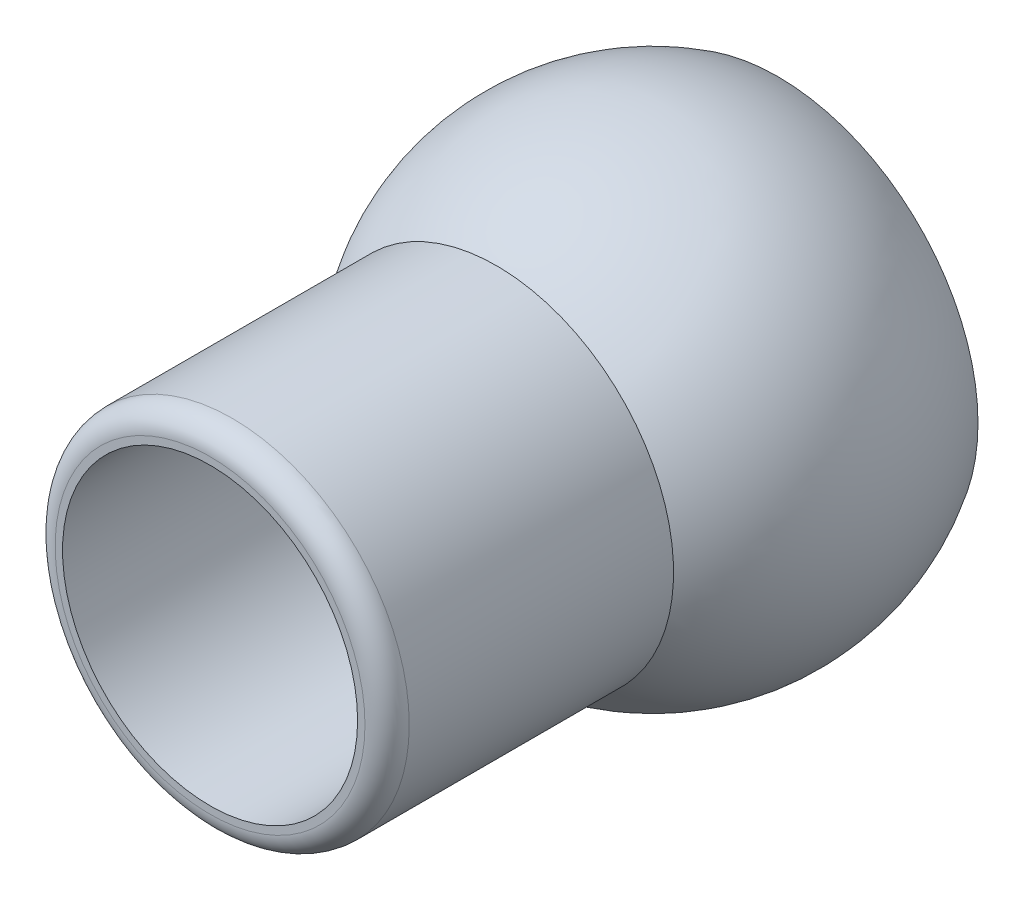
SolidWorks part; units mm, degrees
ref_plane "前视基准面" through (0, 0, 0) normal (0, 0, 1) x (1, 0, 0)
ref_plane "上视基准面" through (0, 0, 0) normal (0, 1, 0) x (1, 0, 0)
ref_plane "右视基准面" through (0, 0, 0) normal (1, 0, 0) x (0, 0, -1)
sketch "草图1" plane through (0, 0, 0) normal (0, 0, 1) x (1, 0, 0)
  line L0 (0, 16) -> (0, -16)
  arc A0 (0, -16) -> (0, 16) centre (0, 0) ccw
revolve "旋转1" add sketch "草图1" angle 360 about L0
sketch "草图2" plane through (0, 0, 0) normal (0, 0, 1) x (1, 0, 0)
  line L0 (0, 14) -> (0, -14)
  arc A0 (0, -14) -> (0, 14) centre (0, 0) ccw
revolve "切除-旋转1" cut sketch "草图2" angle 360 about L0
sketch "草图3" plane through (0, 0, 0) normal (0, 0, 1) x (1, 0, 0)
  circle A0 centre (0, 0) radius 12
extrude "凸台-拉伸2" add sketch "草图3" along normal blind 30
sketch "草图4" plane through (0, 0, 0) normal (0, 0, 1) x (1, 0, 0)
  circle A0 centre (0, 0) radius 10
extrude "切除-拉伸2" cut sketch "草图4" against normal blind 23 and the other way blind 30
sketch "草图6" plane through (0, 0, 0) normal (0, 0, 1) x (1, 0, 0)
  line L0 (0, 14) -> (0, -14)
  arc A0 (0, -14) -> (0, 14) centre (0, 0) ccw
revolve "切除-旋转2" cut sketch "草图6" angle 360 about L0
fillet "圆角1" radius 1.5 1 edges at (12, 0, 30)
sketch "草图7" plane through (0, 0, 0) normal (1, 0, 0) x (0, 0, -1)
  line L0 (0, 0) -> (12.49, 0)
  line L1 (12.49, -10) -> (12.49, 10) construction
  line L2 (12.49, 0) -> (7.49, 0)
  line L3 (7.49, 0) -> (7.49, -16.6991)
  line L4 (7.49, -16.6991) -> (7.49, 14.1386)
  line L5 (7.49, 14.1386) -> (7.49, -14.1386)
  line L6 (7.49, -14.1386) -> (12.49, -14.1386)
  line L7 (12.49, -14.1386) -> (12.49, 14.1386)
  line L8 (12.49, 14.1386) -> (7.49, 14.1386)
  arc A0 (12.49, 10) -> (-10.583, 12) centre (0, 0) ccw construction
  dimension "D1" = 12.49
sketch "草图8" plane through (0, 0, 0) normal (1, 0, 0) x (0, 0, -1)
  line L0 (12.49, -14.1386) -> (8.49, -14.1386)
  line L4 (12.49, 14.1386) -> (12.49, -14.1386)
  line L5 (7.49, -14.1386) -> (12.49, -14.1386) construction
  line L6 (8.49, -14.1386) -> (8.49, 14.1386)
  line L7 (12.49, 14.1386) -> (7.49, 14.1386) construction
  line L8 (8.49, 14.1386) -> (12.49, 14.1386)
  dimension "D1" = 4
extrude "切除-拉伸3" cut sketch "草图8" against normal blind 20 and the other way blind 20
fillet "圆角2" radius 1 1 edges at (-11.1319, 0, -8.49)
sketch "草图9" plane through (0, 0, 0) normal (1, 0, 0) x (0, 0, -1)
  line L0 (7.49, 0) -> (5.49, 0)
  line L1 (0, 0) -> (12.49, 0) construction
  line L2 (5.49, 0) -> (5.49, 15.0286)
  line L3 (5.49, 15.0286) -> (5.49, -15.0286)
  line L4 (5.49, -15.0286) -> (7.49, -15.0286)
  line L5 (7.49, 0) -> (7.49, -16.6991) construction
  line L6 (7.49, -15.0286) -> (7.49, 15.0286)
  line L7 (7.49, 15.0286) -> (5.49, 15.0286)
  arc A0 (8.49, 13.5617) -> (-10.583, 12) centre (0, 0) ccw construction
  arc A1 (-10.583, -12) -> (8.49, -13.5617) centre (0, 0) ccw construction
